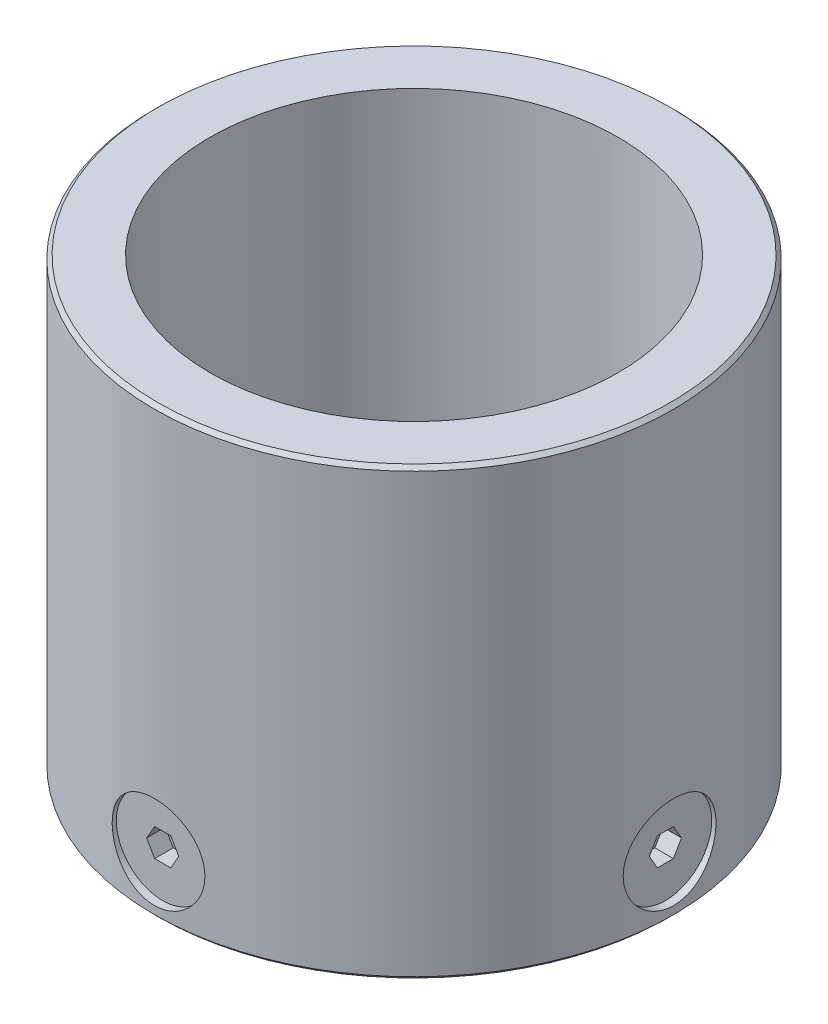
SolidWorks part; units mm, degrees
ref_plane "Спереди" through (0, 0, 0) normal (0, 0, 1) x (1, 0, 0)
ref_plane "Сверху" through (0, 0, 0) normal (0, 1, 0) x (1, 0, 0)
ref_plane "Справа" through (0, 0, 0) normal (1, 0, 0) x (0, 0, -1)
sketch "Эскиз1" plane through (0, 0, 0) normal (0, 1, 0) x (1, 0, 0)
  circle A0 centre (0, 0) radius 11
  circle A1 centre (0, 0) radius 14
  dimension "D1" = 22
  dimension "D2" = 28
extrude "Бобышка-Вытянуть1" add sketch "Эскиз1" along normal blind 24
chamfer "Фаска1" distance 0.2 angle 45 2 edges at (0, 0, 14) (0, 24, 14)
sketch "Эскиз2" plane through (0, 0, 0) normal (1, 0, 0) x (0, 0, -1)
  line L1 (0.866, 3.1274) -> (0.433, 3.8774)
  line L2 (0.433, 3.8774) -> (-0.433, 3.8774)
  line L3 (-0.433, 3.8774) -> (-0.866, 3.1274)
  line L4 (-0.866, 3.1274) -> (-0.433, 2.3774)
  line L5 (-0.433, 2.3774) -> (0.433, 2.3774)
  line L6 (0.433, 2.3774) -> (0.866, 3.1274)
  circle A0 centre (0, 3.1274) radius 2.5
  circle A1 centre (0, 3.1274) radius 0.75 construction
extrude "Вырез-Вытянуть1" cut sketch "Эскиз2" along normal through all contours A0
extrude "Бобышка-Вытянуть2" add sketch "Эскиз2<3>" along normal blind 1.55 from offset 12 separate body contours L5 L6 L1 L2 L3 L4 | A0 L6 L5 L4 L3 L2 L1 region at (0, 3.1274, 0) region at (0, 3.1274, 2.4293)
sketch "Эскиз2<3>" plane through (0, 0, 0) normal (1, 0, 0) x (0, 0, -1) same geometry as "Эскиз2"
extrude "Вырез-Вытянуть2" cut sketch "Эскиз2<4>" against normal blind 1 from surface contours L5 L6 L1 L2 L3 L4 region at (0, 3.1274, 0) starting at face at (13.55, 3.1274, -2.5)
sketch "Эскиз2<4>" plane through (0, 0, 0) normal (1, 0, 0) x (0, 0, -1) same geometry as "Эскиз2"
pattern_circular "Круговой массив1" count 4 over 360 about axis through (0, 24, 0) along (0, -1, 0) of "Вырез-Вытянуть1"
pattern_circular "Круговой массив2" count 4 over 360 about axis through (0, 24, 0) along (0, -1, 0) of bodies 106
